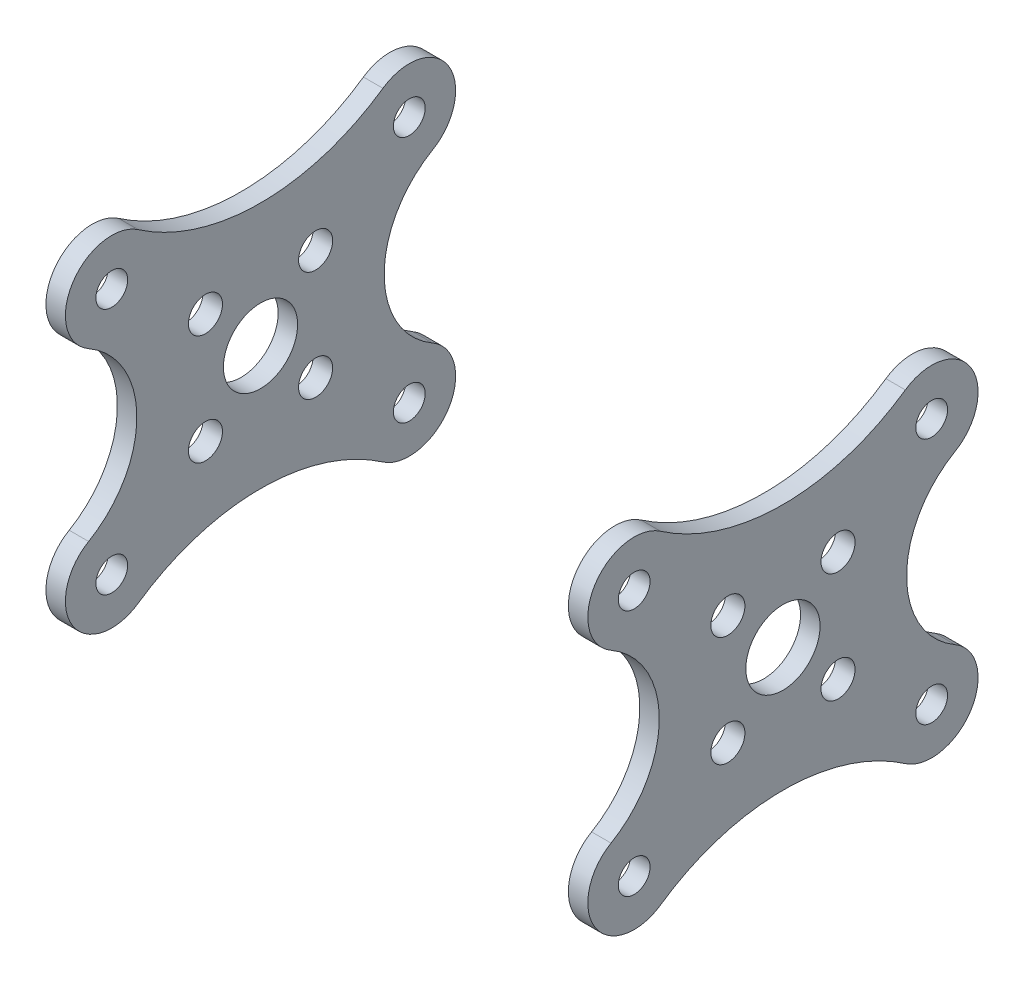
SolidWorks part; units mm, degrees
material "TPU"
ref_plane "Front Plane" through (0, 0, 0) normal (0, 0, 1) x (1, 0, 0)
ref_plane "Top Plane" through (0, 0, 0) normal (0, 1, 0) x (1, 0, 0)
ref_plane "Right Plane" through (0, 0, 0) normal (1, 0, 0) x (0, 0, -1)
ref_plane "Plane2" through (27.825, 0, 0) normal (1, 0, 0) x (0, 0, -1)
sketch "Sketch1" plane through (27.825, 0, 0) normal (1, 0, 0) x (0, 0, -1)
  line L0 (0, 15.875) -> (-97.3726, 15.875) construction
  circle A0 centre (-45.0415, 12.7) radius 3.175 construction
  circle A1 centre (-14.4897, 12.7) radius 3.175 construction
  circle A2 centre (-14.4897, -12.7) radius 3.175 construction
  circle A3 centre (-45.0415, -12.7) radius 3.175 construction
  circle A4 centre (-45.0415, 12.7) radius 4.3656 construction
  circle A5 centre (-14.4897, 12.7) radius 4.3656 construction
  circle A6 centre (-14.4897, -12.7) radius 4.3656 construction
  circle A7 centre (-45.0415, -12.7) radius 4.3656 construction
  circle A8 centre (-45.0415, 12.7) radius 1.4224 construction
  circle A9 centre (-29.7656, 0) radius 12.7 construction
  arc A10 (-17.1962, 16.6187) -> (-12.1114, 8.5739) centre (-14.4897, 12.7) cw
  arc A11 (-12.1114, -8.5739) -> (-17.1962, -16.6187) centre (-14.4897, -12.7) cw
  arc A12 (-42.335, -16.6187) -> (-47.4198, -8.5739) centre (-45.0415, -12.7) cw
  arc A13 (-47.4198, 8.5739) -> (-42.335, 16.6187) centre (-45.0415, 12.7) cw
  circle A14 centre (-29.7656, 0) radius 15.5 construction
  arc A15 (-47.4198, 8.5739) -> (-47.4198, -8.5739) centre (-52.3618, 0) cw
  arc A16 (-12.1114, -8.5739) -> (-12.1114, 8.5739) centre (-7.1695, 0) cw
  arc A17 (-42.335, 16.6187) -> (-17.1962, 16.6187) centre (-29.7656, 34.8178) ccw
  arc A18 (-42.335, -16.6187) -> (-17.1962, -16.6187) centre (-29.7656, -34.8178) cw
  circle A21 centre (-29.7656, 0) radius 15.5 construction
  dimension "D1" = 6.35
  dimension "D2" = 1.1906
  dimension "D3" = 2.8448
  dimension "D4" = 1.5875
  dimension "D5" = 25.4
extrude "Boss-Extrude1" add sketch "Sketch1" against normal blind 2
sketch "Sketch2" plane through (25.825, 0, 0) normal (-1, 0, 0) x (0, 0, 1)
  line L0 (52.3618, 0) -> (7.1695, 0) construction
  line L3 (29.7656, 12.7) -> (29.7656, -12.7) construction
  line L7 (24.1088, -5.6569) -> (35.4225, 5.6569) construction
  line L8 (24.1088, 5.6569) -> (35.4225, -5.6569) construction
  circle A1 centre (24.1088, 5.6569) radius 1.75
  circle A2 centre (24.1088, -5.6569) radius 1.75
  circle A3 centre (35.4225, -5.6569) radius 1.75
  circle A4 centre (35.4225, 5.6569) radius 1.75
  arc A5 (47.4198, 8.5739) -> (47.4198, -8.5739) centre (52.3618, 0) ccw construction
  arc A6 (12.1114, -8.5739) -> (12.1114, 8.5739) centre (7.1695, 0) ccw construction
  arc A7 (17.1962, 16.6187) -> (42.335, 16.6187) centre (29.7656, 34.8178) ccw construction
  circle A8 centre (29.7656, 0) radius 3.81
  point P16 (29.7656, 0)
  dimension "D4" = 3.5
  dimension "D5" = 7.62
  dimension "D1" = 16
  dimension "D2" = 16
  dimension "D3" = 45
extrude "Cut-Extrude1" cut sketch "Sketch2" against normal up to surface (2 mm away) up to face at (27.825, 0, 29.7656)
sketch "Sketch4" [suppressed] plane through (25.92, 0, 0) normal (1, 0, 0) x (0, 0, -1)
  circle A0 centre (-14.4897, 12.7) radius 4.7625
  circle A1 centre (-45.0415, 12.7) radius 4.7625
  circle A2 centre (-45.0415, -12.7) radius 4.7625
  circle A3 centre (-14.4897, -12.7) radius 4.7625
  arc A4 (-15.6935, -17.3078) -> (-10.8058, -9.6817) centre (-14.4897, -12.7) ccw construction
  arc A5 (-10.8058, 9.6817) -> (-15.6935, 17.3078) centre (-14.4897, 12.7) ccw construction
  arc A6 (-43.8377, 17.3078) -> (-48.7254, 9.6817) centre (-45.0415, 12.7) ccw construction
  arc A7 (-48.7254, -9.6817) -> (-43.8377, -17.3078) centre (-45.0415, -12.7) ccw construction
extrude "Boss-Extrude2" [suppressed] add sketch "Sketch4" against normal up to surface (11.43 mm away)
fillet "Fillet1" [suppressed] radius 2.54
hole_wizard "#4 Clearance Hole1" positions "Sketch6" profile "Sketch8" hole size "#4" standard "ANSI Inch" end condition up to next
sketch "Sketch6" plane through (25.825, 0, 0) normal (1, 0, 0) x (0, 0, -1)
  arc A0 (-42.335, 16.6187) -> (-47.4198, 8.5739) centre (-45.0415, 12.7) ccw construction
  arc A1 (-12.1114, 8.5739) -> (-17.1962, 16.6187) centre (-14.4897, 12.7) ccw construction
  arc A2 (-17.1962, -16.6187) -> (-12.1114, -8.5739) centre (-14.4897, -12.7) ccw construction
  arc A3 (-47.4198, -8.5739) -> (-42.335, -16.6187) centre (-45.0415, -12.7) ccw construction
  point P0 (-45.0415, 12.7)
  point P3 (-14.4897, 12.7)
  point P6 (-14.4897, -12.7)
  point P9 (-45.0415, -12.7)
sketch "Sketch8" plane through (25.825, 12.7, 45.0415) normal (0, 1, 0) x (0, 0, 1)
  line L0 (0, 0) -> (0, 2)
  line L1 (0, 2) -> (1.6319, 2)
  line L2 (1.6319, 2) -> (1.6319, 0)
  line L5 (1.6319, 0) -> (0, 0)
  line L11 (0, -6.35) -> (0, 107.95) construction
  dimension "Thru Hole Dia." = 3.2639
  dimension "Thru Hole Depth" = 2
chamfer "Chamfer1" [suppressed] distance 2.032 angle 45
mirror "Mirror1" about plane through (0, 0, 0) normal (1, 0, 0) of bodies 106 104
equation "\"D1@Sketch2\"=16mm"
equation "\"D2@Sketch2\"=16mm"
equation "\"D1@Boss-Extrude1\"=2mm"
